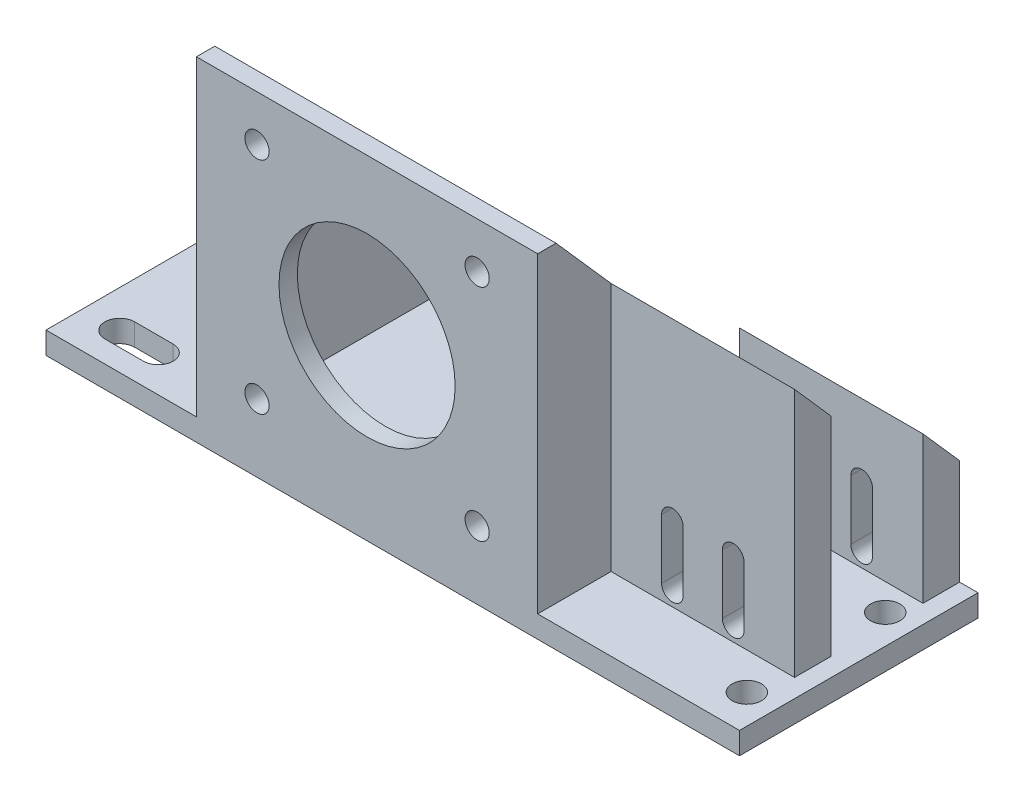
SolidWorks part; units mm, degrees
ref_plane "Front Plane" through (0, 0, 0) normal (0, 0, 1) x (1, 0, 0)
ref_plane "Top Plane" through (0, 0, 0) normal (0, 1, 0) x (1, 0, 0)
ref_plane "Right Plane" through (0, 0, 0) normal (1, 0, 0) x (0, 0, -1)
sketch "Sketch1" plane through (0, 0, 0) normal (0, 1, 0) x (1, 0, 0)
  line L0 (41, 40) -> (41, 0) construction
  line L1 (0, 0) -> (82, 0)
  line L2 (0, 0) -> (0, 40)
  line L3 (0, 40) -> (82, 40)
  line L4 (82, 0) -> (82, 40)
  line L5 (41, 20) -> (18, 20) construction
  line L6 (82, 14.3756) -> (74, 14.3756) construction
  line L7 (18, 40) -> (18, 0) construction
  line L8 (74, 40) -> (74, 0) construction
  line L9 (-7.5, 23.86) -> (-2.25, 23.86) construction
  line L10 (0, 40) -> (-12.5, 40)
  line L11 (0, 40) -> (0, 0)
  line L12 (0, 0) -> (-12.5, 0)
  line L13 (-12.5, 40) -> (-12.5, 0)
  line L14 (-7.5, 25.885) -> (-2.25, 25.885)
  line L15 (-7.5, 21.835) -> (-2.25, 21.835)
  line L17 (-7.4329, 4.985) -> (-2.1829, 4.985) construction
  line L18 (-7.4329, 7.01) -> (-2.1829, 7.01)
  line L19 (-7.4329, 2.96) -> (-2.1829, 2.96)
  arc A0 (-7.4329, 7.01) -> (-7.4329, 2.96) centre (-7.4329, 4.985) ccw
  circle A1 centre (4, 23.86) radius 2 construction
  circle A2 centre (4, 5) radius 2 construction
  circle A4 centre (78, 23.86) radius 2
  circle A5 centre (78, 5) radius 2
  arc A6 (-7.5, 25.885) -> (-7.5, 21.835) centre (-7.5, 23.86) ccw
  arc A7 (-2.25, 21.835) -> (-2.25, 25.885) centre (-2.25, 23.86) ccw
  arc A8 (-2.1829, 2.96) -> (-2.1829, 7.01) centre (-2.1829, 4.985) ccw
  point P29 (-4.875, 23.86)
  point P37 (-4.8079, 4.985)
  dimension "D3" = 4
  dimension "D7" = 4.05
  dimension "D14" = 5.25
  dimension "D15" = 4.05
  dimension "D16" = 18.875
  dimension "D1" = 82
  dimension "D2" = 40
  dimension "D4" = 4
  dimension "D5" = 4
  dimension "D6" = 12.5
  dimension "D8" = 18.86
  dimension "D9" = 5
  dimension "D10" = 23
  dimension "D11" = 8
  dimension "D12" = 5
  dimension "D13" = 5.25
extrude "Boss-Extrude1" add sketch "Sketch1" along normal blind 3 contours L1 L4 L3 L2 A4 A5 | L10 L13 L12 L2 region at (40.7143, 0, -20.043) region at (-6.4728, 0, -20.8823)
sketch "Sketch2" plane through (0, 3, 0) normal (0, 1, 0) x (1, 0, 0)
  line L0 (10, 40) -> (10, 0)
  line L4 (8, 40) -> (8, 0)
  line L5 (54.5, 40) -> (54.5, 0)
  line L6 (52.5, 40) -> (52.5, 0)
  line L7 (10, 2.5) -> (52.5, 2.5)
  line L9 (-12.5, 0) -> (82, 0)
  line L10 (82, 0) -> (82, 40)
  line L11 (82, 40) -> (-12.5, 40)
  line L12 (-12.5, 40) -> (-12.5, 0)
  line L13 (-12.5, 0) -> (82, 0)
  line L14 (82, 0) -> (82, 40)
  line L15 (82, 40) -> (-12.5, 40)
  line L16 (-12.5, 40) -> (-12.5, 0)
  dimension "D2" = 42.5
  dimension "D3" = 2
  dimension "D4" = 2
  dimension "D5" = 2.5
  dimension "D6" = 27.5
  dimension "D1" = 0
extrude "Boss-Extrude2" add sketch "Sketch2" along normal blind 42.5 contours L0 L15 L4 L13 | L0 L13 L6 L7 | L5 L15 L6 L13 region at (9, 3, -20) region at (31.25, 3, -1.25) region at (53.5, 3, -20)
sketch "Sketch3" plane through (54.5, 6, 0) normal (-1, 0, 0) x (0, 0, -1)
  line L1 (40, -39.5) -> (0, -39.5)
  line L2 (2.5, -39.5) -> (40, 3)
  line L5 (0, 3) -> (40, 3)
  line L7 (40, 3) -> (0, 3)
  line L8 (40, -39.5) -> (40, 3)
  line L9 (0, -39.5) -> (40, -39.5)
  line L10 (0, 3) -> (0, -39.5)
  line L11 (40, 3) -> (0, 3)
  line L12 (40, -39.5) -> (40, 3)
  line L13 (0, -39.5) -> (40, -39.5)
  line L14 (0, 3) -> (0, -39.5)
  line M30 (40, 3) -> (40, -39.5)
  line M31 (40, -39.5) -> (0, -39.5)
  dimension "D2" = 40
  dimension "D1" = 56.6789
  dimension "D3" = 0
extrude "Cut-Extrude1" cut sketch "Sketch3" along normal through all contours L2 M31 M30 region at (54.5, 31.3333, -27.5)
sketch "Sketch4" plane through (0, 0, 0) normal (0, 0, 1) x (1, 0, 0)
  line L0 (10, 45.5) -> (52.5, 3) construction
  line L1 (52.5, 45.5) -> (10, 3) construction
  line L6 (10, 3) -> (52.5, 3)
  line L7 (10, 45.5) -> (10, 3)
  line L8 (52.5, 45.5) -> (10, 45.5)
  line L9 (52.5, 3) -> (52.5, 45.5)
  line L10 (10, 3) -> (52.5, 3)
  line L11 (10, 45.5) -> (10, 3)
  line L12 (52.5, 45.5) -> (10, 45.5)
  line L13 (52.5, 3) -> (52.5, 45.5)
  circle A0 centre (31.25, 24.25) radius 12
  circle A1 centre (16.25, 39.25) radius 1.65
  circle A2 centre (16.25, 9.25) radius 1.65
  circle A3 centre (46.25, 9.25) radius 1.65
  circle A4 centre (46.25, 39.25) radius 1.65
  dimension "D2" = 24
  dimension "D3" = 3.3
  dimension "D4" = 30
  dimension "D1" = 0
extrude "Cut-Extrude2" cut sketch "Sketch4" against normal through all contours A0 | A2 | A1 | A4 | A3 region at (31.25, 24.25, 0)
sketch "Sketch7" plane through (0, 3, 0) normal (0, 1, 0) x (1, 0, 0)
  line L0 (54.5, 10) -> (79.5, 10)
  line L2 (79.5, 10) -> (79.5, 15)
  line L3 (79.5, 15) -> (54.5, 15)
  line L4 (54.5, 15) -> (54.5, 27.5)
  line L5 (54.5, 27.5) -> (79.5, 27.5)
  line L6 (79.5, 27.5) -> (79.5, 32.5)
  line L7 (79.5, 32.5) -> (54.5, 32.5)
  line L8 (54.5, 40) -> (54.5, 32.5)
  line L13 (82, 40) -> (54.5, 40)
  line L14 (54.5, 40) -> (54.5, 0)
  line L15 (54.5, 0) -> (82, 0)
  line L16 (82, 40) -> (54.5, 40)
  line L17 (54.5, 10) -> (54.5, 0)
  line L18 (54.5, 0) -> (82, 0)
  line L19 (82, 0) -> (82, 40)
  line L20 (82, 0) -> (82, 40)
  line L21 (82, 40) -> (54.5, 40)
  line L22 (54.5, 40) -> (54.5, 0)
  line L23 (54.5, 0) -> (82, 0)
  line L24 (82, 0) -> (82, 40)
  line M37 (54.5, 40) -> (54.5, 0)
  dimension "D2" = 5
  dimension "D3" = 5
  dimension "D5" = 7.5
  dimension "D1" = 0
extrude "Boss-Extrude3" add sketch "Sketch7" along normal blind 20 contours L6 L7 L5 region at (67, 3, -30)
extrude "Boss-Extrude4" add sketch "Sketch7<3>" along normal up to surface (34 mm away) contours L2 L3 L0 M37 region at (67, 3, -12.5) up to face at (53.8333, 20.9444, -24.1667)
sketch "Sketch7<3>" plane through (0, 3, 0) normal (0, 1, 0) x (1, 0, 0) same geometry as "Sketch7"
sketch "Sketch9" plane through (0, 0, -10) normal (0, 0, 1) x (1, 0, 0)
  line L0 (62.8561, 13.1701) -> (62.8561, 5.0521) construction
  line L1 (64.3301, 13.1701) -> (64.3301, 5.0521)
  line L2 (61.3822, 13.1701) -> (61.3822, 5.0521)
  line L3 (67, 37) -> (67, 3) construction
  line L8 (54.5, 3) -> (79.5, 3) construction
  line L9 (71.1439, 13.1701) -> (71.1439, 5.0521) construction
  line L10 (69.6699, 13.1701) -> (69.6699, 5.0521)
  line L11 (72.6178, 13.1701) -> (72.6178, 5.0521)
  arc A0 (64.3301, 13.1701) -> (61.3822, 13.1701) centre (62.8561, 13.1701) ccw
  arc A1 (61.3822, 5.0521) -> (64.3301, 5.0521) centre (62.8561, 5.0521) ccw
  arc A2 (69.6699, 13.1701) -> (72.6178, 13.1701) centre (71.1439, 13.1701) cw
  arc A3 (72.6178, 5.0521) -> (69.6699, 5.0521) centre (71.1439, 5.0521) cw
  point P2 (62.8561, 9.1111)
  point P14 (71.1439, 9.1111)
  point P15 (67, 37)
extrude "Cut-Extrude3" cut sketch "Sketch9" against normal through all contours L2 A1 L1 A0 | A3 L11 A2 L10 region at (62.8561, 9.1111, -10) region at (71.1439, 9.1111, -10)
sketch "Sketch11" plane through (54.5, 0, 0) normal (-1, 0, 0) x (0, 0, 1)
  line L0 (-27.5, 23) -> (-32.5, 17.3326)
  line L1 (-32.5, 23) -> (-32.5, 11.5) construction
  line L6 (-32.5, 23) -> (-32.5, 11.5)
  line L7 (-32.5, 11.5) -> (-27.5, 17.1667)
  line L8 (-27.5, 17.1667) -> (-27.5, 23)
  line L9 (-27.5, 23) -> (-32.5, 23)
  line L10 (-32.5, 23) -> (-32.5, 11.5)
  line L11 (-32.5, 11.5) -> (-27.5, 17.1667)
  line L12 (-27.5, 17.1667) -> (-27.5, 23)
  line L13 (-27.5, 23) -> (-32.5, 23)
  line M2 (-32.5, 23) -> (-32.5, 11.5)
  line M5 (-27.5, 23) -> (-32.5, 23)
  dimension "D2" = 41.424
  dimension "D3" = 41.42
  dimension "D1" = 0
extrude "Cut-Extrude4" cut sketch "Sketch11" against normal through all contours L0 M5 M2 region at (54.5, 21.1109, -30.8333)
sketch "Sketch13" plane through (0, 3, 0) normal (0, 1, 0) x (1, 0, 0)
  line L0 (-12.5, 40) -> (-12.5, 0) construction
  line L1 (82, 40) -> (-12.5, 40)
  line L2 (82, 40) -> (82, 32.5)
  line L3 (82, 32.5) -> (-12.5, 32.5)
  line L4 (-12.5, 40) -> (-12.5, 32.5)
  point P7 (82, 32.5)
extrude "Cut-Extrude5" cut sketch "Sketch13" against normal through all and the other way through all
